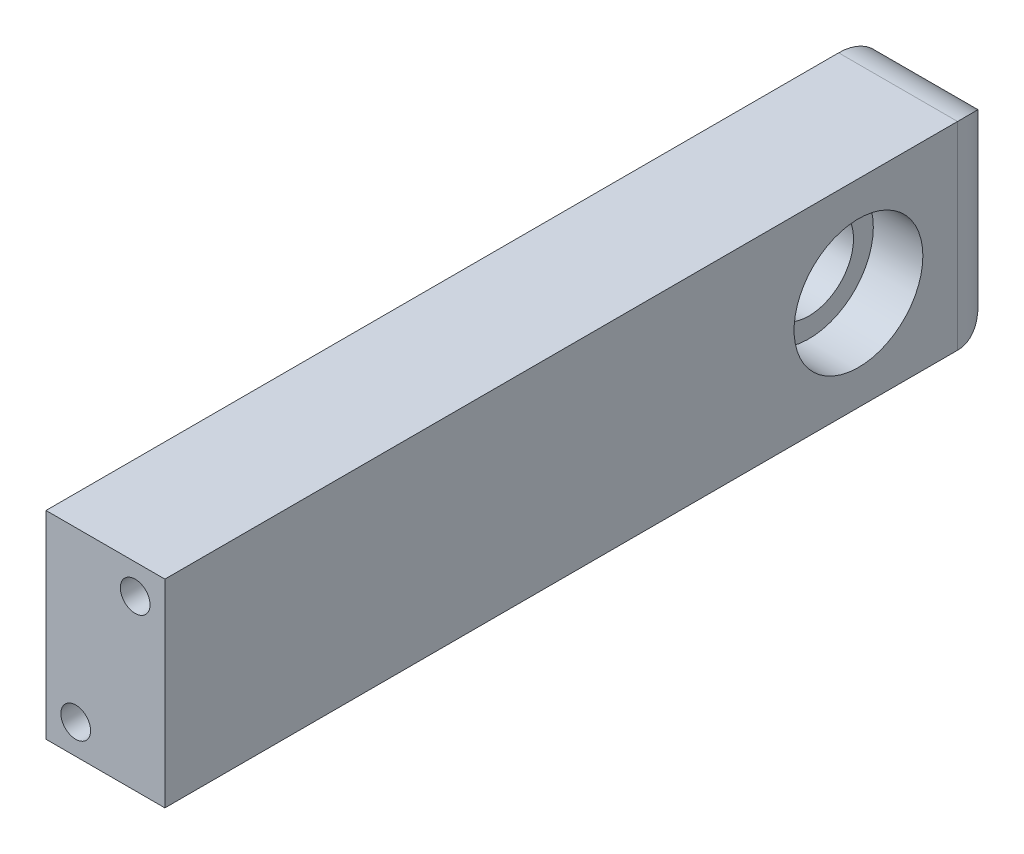
SolidWorks part; units mm, degrees
ref_plane "Płaszczyzna przednia" through (0, 0, 0) normal (0, 0, 1) x (1, 0, 0)
ref_plane "Płaszczyzna górna" through (0, 0, 0) normal (0, 1, 0) x (1, 0, 0)
ref_plane "Płaszczyzna prawa" through (0, 0, 0) normal (1, 0, 0) x (0, 0, -1)
sketch "Szkic1" plane through (0, 0, 0) normal (0, 0, 1) x (1, 0, 0)
  line L1 (-6, -10) -> (6, -10)
  line L2 (-6, -10) -> (-6, 10)
  line L3 (-6, 10) -> (6, 10)
  line L4 (6, -10) -> (6, 10)
  line L5 (-6, -10) -> (6, 10) construction
  line L6 (-6, 10) -> (6, -10) construction
  point P0 (0, 0)
  dimension "D1" = 20
  dimension "D2" = 12
extrude "Dodanie-wyciągnięcie1" add sketch "Szkic1" along normal blind 85
sketch "Szkic2" plane through (0, 0, 85) normal (0, 0, 1) x (1, 0, 0)
  line L0 (6, -10) -> (6, 10) construction
  line L3 (6, 10) -> (-6, 10) construction
  line L5 (-6, -10) -> (6, -10) construction
  line L6 (-6, 10) -> (-6, -10) construction
  circle A0 centre (3, 7) radius 1.5
  circle A1 centre (-3, -7) radius 1.5
  dimension "D1" = 3
  dimension "D2" = 3
  dimension "D3" = 3
  dimension "D4" = 3
  dimension "D5" = 3
  dimension "D6" = 3
extrude "Wytnij-wyciągnięcie1" cut sketch "Szkic2" against normal blind 10
sketch "Szkic5" plane through (6, 0, 0) normal (1, 0, 0) x (0, 0, -1)
  line L0 (-85, -10) -> (0, -10) construction
  line L1 (-85, -10) -> (-85, 10) construction
  circle A0 centre (-15, 0) radius 6.5
  dimension "D1" = 13
  dimension "D2" = 10
  dimension "D3" = 70
extrude "Wytnij-wyciągnięcie4" cut sketch "Szkic5" against normal blind 5
sketch "Szkic6" plane through (-6, 0, 0) normal (-1, 0, 0) x (0, 0, 1)
  line L0 (85, -10) -> (0, -10) construction
  line L1 (85, 10) -> (85, -10) construction
  circle A0 centre (15, 0) radius 4.5
  dimension "D1" = 9
  dimension "D2" = 10
  dimension "D3" = 70
extrude "Wytnij-wyciągnięcie5" cut sketch "Szkic6" against normal through all
fillet "Zaokrąglenie1" radius 5 3 edges at (0, -10, 0) (6, 0, 0) (0, 10, 0)
